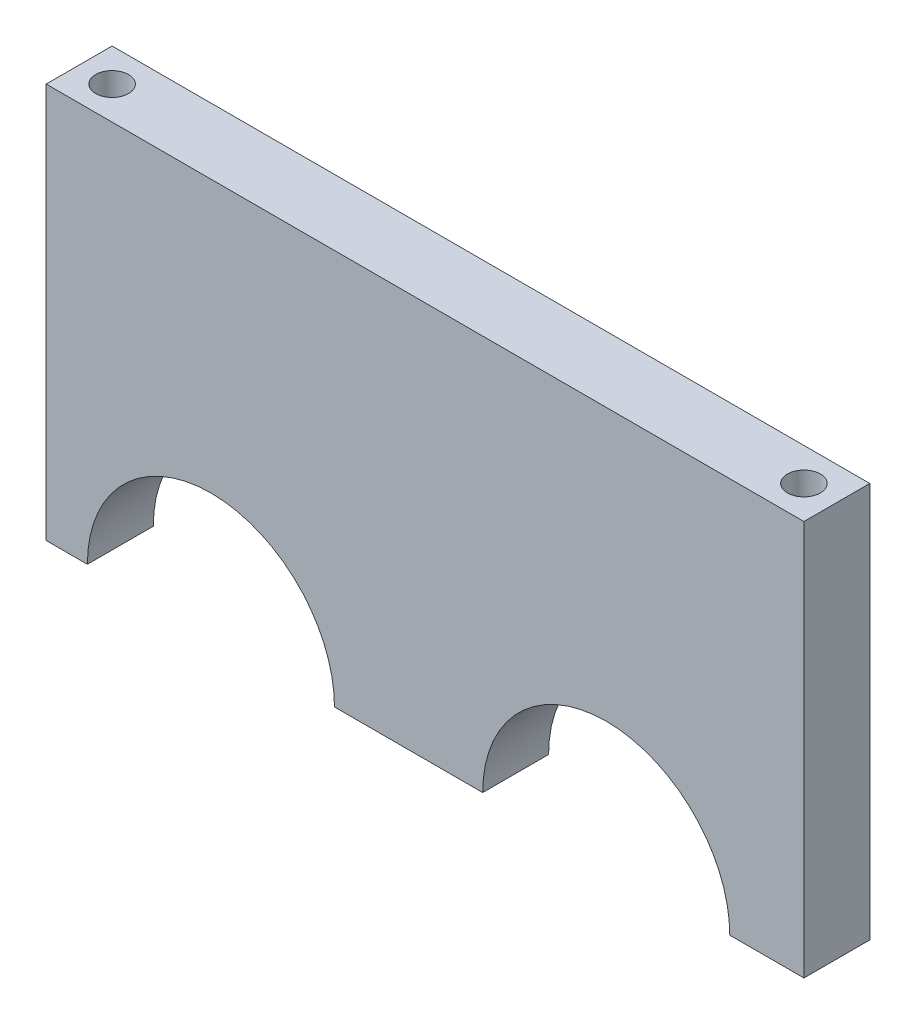
SolidWorks part; units mm, degrees
ref_plane "Front Plane" through (0, 0, 0) normal (0, 0, 1) x (1, 0, 0)
ref_plane "Top Plane" through (0, 0, 0) normal (0, 1, 0) x (1, 0, 0)
ref_plane "Right Plane" through (0, 0, 0) normal (1, 0, 0) x (0, 0, -1)
sketch "Sketch1" plane through (0, 0, 0) normal (0, 0, 1) x (1, 0, 0)
  line L1 (0, 0) -> (230, 0)
  line L2 (0, 0) -> (0, 120)
  line L3 (0, 120) -> (230, 120)
  line L4 (230, 0) -> (230, 120)
  dimension "D1" = 230
  dimension "D2" = 120
extrude "Boss-Extrude1" add sketch "Sketch1" along normal blind 20
sketch "Sketch2" plane through (0, 0, 20) normal (0, 0, 1) x (1, 0, 0)
  line L0 (0, 0) -> (230, 0) construction
  line L1 (0, 120) -> (0, 0) construction
  line L2 (230, 0) -> (230, 120) construction
  circle A0 centre (50, 0) radius 37.5
  circle A1 centre (170, 0) radius 37.5
  dimension "D1" = 75
  dimension "D2" = 75
  dimension "D3" = 50
  dimension "D4" = 60
extrude "Cut-Extrude1" cut sketch "Sketch2" against normal through all
sketch "Sketch3" plane through (0, 120, 0) normal (0, 1, 0) x (1, 0, 0)
  line L0 (230, -20) -> (230, 0) construction
  line L1 (230, 0) -> (0, 0) construction
  line L2 (230, -20) -> (0, -20) construction
  line L4 (0, -20) -> (0, 0) construction
  circle A0 centre (220, -10) radius 5
  circle A1 centre (10, -10) radius 5
  point P12 (0, -10.5201)
  point P13 (90.849, -5.6896)
  dimension "D1" = 10
  dimension "D4" = 10
  dimension "D2" = 10
  dimension "D3" = 10
  dimension "D5" = 10
  dimension "D6" = 10
extrude "Cut-Extrude2" cut sketch "Sketch3" against normal blind 20
sketch "Sketch4" plane through (0, 120, 0) normal (0, 1, 0) x (1, 0, 0)
  line L0 (230, 200) -> (0, 200) construction
  line L1 (230, 190) -> (230, 210) construction
  line L2 (0, 190) -> (0, 210) construction
  point P6 (115, 200)
